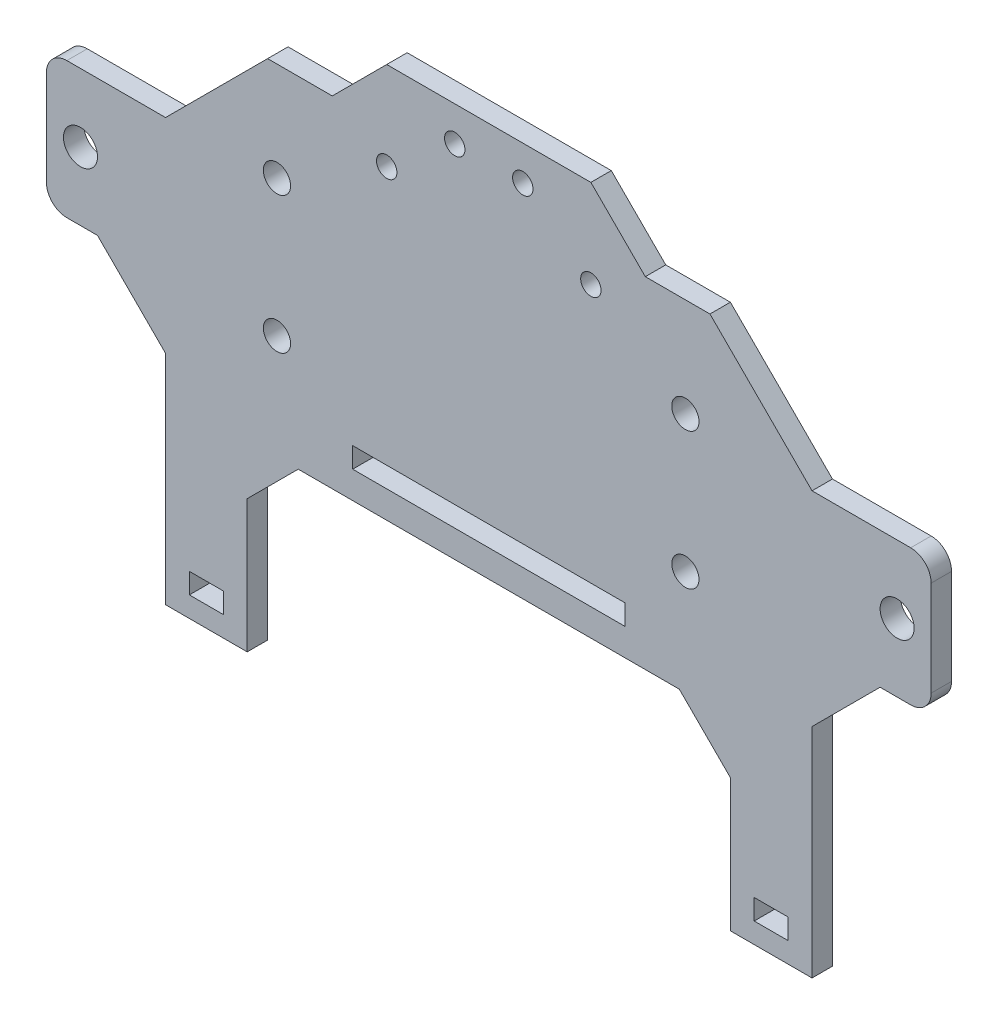
SolidWorks part; units mm, degrees
ref_plane "Front" through (0, 0, 0) normal (0, 0, 1) x (1, 0, 0)
ref_plane "Top" through (0, 0, 0) normal (0, 1, 0) x (1, 0, 0)
ref_plane "Right" through (0, 0, 0) normal (1, 0, 0) x (0, 0, -1)
sketch "Sketch1" plane through (0, 0, 0) normal (0, 0, 1) x (1, 0, 0)
  line L0 (40.5, -40) -> (44.5, -40)
  line L1 (44.5, -40) -> (47.5, -37)
  line L2 (47.5, -37) -> (47.5, 10)
  line L3 (52.5, 15) -> (70, 15)
  line L4 (75, 20) -> (75, 60)
  line L5 (70, 65) -> (-70, 65)
  line L6 (-75, 60) -> (-75, 20)
  line L7 (-70, 15) -> (-52.5, 15)
  line L8 (-47.5, 10) -> (-47.5, -37)
  line L9 (-47.5, -37) -> (-44.5, -40)
  line L10 (-44.5, -40) -> (-40.5, -40)
  line L11 (-40.5, -40) -> (-37.5, -37)
  line L12 (-37.5, -37) -> (-37.5, 10)
  line L13 (-32.5, 15) -> (32.5, 15)
  line L14 (37.5, 10) -> (37.5, -37)
  line L15 (37.5, -37) -> (40.5, -40)
  line L16 (0, 15) -> (0, 65) construction
  line L17 (-52.5, 15) -> (-47.5, 15)
  line L18 (-47.5, 15) -> (-47.5, 10)
  line L19 (52.5, 15) -> (47.5, 15)
  line L20 (47.5, 15) -> (47.5, 10)
  circle A0 centre (-42.5, -20) radius 1.5
  circle A1 centre (-42.5, -35) radius 1.5
  circle A2 centre (42.5, -20) radius 1.5
  circle A3 centre (42.5, -35) radius 1.5
  arc A5 (70, 15) -> (75, 20) centre (70, 20) ccw
  arc A6 (75, 60) -> (70, 65) centre (70, 60) ccw
  arc A7 (-70, 65) -> (-75, 60) centre (-70, 60) ccw
  arc A8 (-75, 20) -> (-70, 15) centre (-70, 20) ccw
  arc A10 (-32.5, 15) -> (-37.5, 10) centre (-32.5, 10) ccw
  arc A11 (37.5, 10) -> (32.5, 15) centre (32.5, 10) ccw
  circle A12 centre (60, 40) radius 2.5
  circle A14 centre (15, 60) radius 1.5
  circle A15 centre (-15, 60) radius 1.5
  circle A17 centre (-60, 40) radius 2.5
  point P28 (42.5, -9.2526)
  dimension "D2" = 5
  dimension "D3" = 15
  dimension "D4" = 3
  dimension "D7" = 15
  dimension "D8" = 5
  dimension "D10" = 5
  dimension "D15" = 5
  dimension "D17" = 5
  dimension "D1" = 150
  dimension "D11" = 50
  dimension "D12" = 27.5
  dimension "D13" = 140
  dimension "D14" = 40
  dimension "D16" = 40
  dimension "D18" = 5
  dimension "D19" = 5
extrude "Boss-Extrude1" add sketch "Sketch1" along normal blind 3
sketch "Sketch3" plane through (0, 0, 3) normal (0, 0, 1) x (1, 0, 0)
  line L0 (75, 27.5) -> (84.1937, 27.5) construction
  line L1 (65, 50) -> (65, 30)
  line L2 (75, 32.3641) -> (75, 23.0348)
  line L3 (47.5, 15) -> (75, 15)
  line L4 (47.5, 15) -> (47.5, 30)
  line L5 (47.5, 30) -> (65, 30)
  line L6 (75, 15) -> (75, 23.0348)
  line L7 (75, 65) -> (75, 32.3641)
  line L8 (47.5, 50) -> (65, 50)
  line L9 (47.5, 65) -> (47.5, 50)
  line L10 (47.5, 65) -> (75, 65)
  line L11 (0, 15) -> (0, 24.3681) construction
  line L12 (-32.5, 15) -> (32.5, 15) construction
  line L13 (-75, 27.5) -> (-84.1937, 27.5) construction
  line L14 (-47.5, 65) -> (-75, 65)
  line L15 (-47.5, 65) -> (-47.5, 50)
  line L16 (-47.5, 50) -> (-65, 50)
  line L17 (-75, 65) -> (-75, 32.3641)
  line L18 (-75, 15) -> (-75, 23.0348)
  line L19 (-47.5, 30) -> (-65, 30)
  line L20 (-47.5, 15) -> (-47.5, 30)
  line L21 (-47.5, 15) -> (-75, 15)
  line L24 (-75, 32.3641) -> (-75, 23.0348)
  line L26 (-65, 50) -> (-65, 30)
  dimension "D2" = 10
  dimension "D3" = 27.5
  dimension "D4" = 50
  dimension "D5" = 15
extrude "Cut-Extrude1" cut sketch "Sketch3" against normal blind 3
fillet "Fillet1" radius 3 4 edges at (65, 50, 1.5) (65, 30, 1.5) (-65, 50, 1.5) (-65, 30, 1.5)
chamfer "Chamfer4" distance 15 angle 45 2 edges at (47.5, 65, 1.5) (-47.5, 65, 1.5)
chamfer "Chamfer5" distance 10 angle 45 2 edges at (47.5, 30, 1.5) (-47.5, 30, 1.5)
sketch "Sketch6" plane through (0, 0, 3) normal (0, 0, 1) x (1, 0, 0)
  line L0 (-62, 50) -> (-47.5, 63)
  line L1 (-47.5, 63) -> (-32.5, 65)
  line L2 (0, 65) -> (0, 56.0032) construction
  line L3 (32.5, 65) -> (-32.5, 65) construction
  line L4 (-62, 50) -> (-47.5, 50) construction
  line L5 (-32.5, 65) -> (-47.5, 50) construction
  line L6 (-62, 50) -> (-47.5, 50)
  line L7 (-32.5, 65) -> (-47.5, 50)
  line L8 (32.5, 65) -> (47.5, 50)
  line L9 (62, 50) -> (47.5, 50)
  line L10 (47.5, 63) -> (32.5, 65)
  line L11 (62, 50) -> (47.5, 63)
  dimension "D1" = 13
sketch "Sketch13" plane through (0, 0, 3) normal (0, 0, 1) x (1, 0, 0)
  line L0 (32.5, 65) -> (-32.5, 65) construction
  line L1 (-15, 65) -> (15, 65)
  line L2 (-15, 65) -> (-15, 73)
  line L3 (-15, 73) -> (15, 73)
  line L4 (15, 65) -> (15, 73)
  dimension "D1" = 8
extrude "Boss-Extrude5" add sketch "Sketch13" against normal blind 3
sketch "Sketch8" plane through (0, 0, 3) normal (0, 0, 1) x (1, 0, 0)
  line L1 (-47.5, 20) -> (47.5, 20)
  line L2 (-47.5, 20) -> (-47.5, -45.3047)
  line L3 (-47.5, -45.3047) -> (47.5, -45.3047)
  line L4 (47.5, 20) -> (47.5, -45.3047)
extrude "Cut-Extrude5" cut sketch "Sketch8" against normal blind 10
sketch "Sketch11" plane through (0, 0, 3) normal (0, 0, 1) x (1, 0, 0)
  line L1 (-47.5, 20) -> (47.5, 20)
  line L2 (-47.5, 20) -> (-47.5, 13)
  line L3 (-47.5, 13) -> (47.5, 13)
  line L4 (47.5, 20) -> (47.5, 13)
  dimension "D1" = 7
extrude "Boss-Extrude3" add sketch "Sketch11" against normal blind 3
sketch "Sketch10" plane through (0, 0, 3) normal (0, 0, 1) x (1, 0, 0)
  line L7 (0, 63.3) -> (0, 65) construction
  line L10 (-47.5, 13) -> (47.5, 13) construction
  line L11 (-30, 13) -> (-28, 15)
  line L12 (-28, 15) -> (28, 15)
  line L13 (28, 15) -> (30, 13)
  line L14 (-30, 13) -> (30, 13)
  circle A0 centre (5, 67.89) radius 1.5
  circle A1 centre (-5, 67.89) radius 1.5
  circle A2 centre (-5, 18.11) radius 1.5
  circle A3 centre (5, 18.11) radius 1.5
  point P0 (0, 43)
  dimension "D4" = 3
  dimension "D5" = 5
  dimension "D3" = 30
  dimension "D7" = 2
  dimension "D8" = 30
  dimension "D9" = 30
  dimension "D10" = 2
extrude "Cut-Extrude6" cut sketch "Sketch10" against normal blind 3
sketch "Sketch12" plane through (0, 0, 3) normal (0, 0, 1) x (1, 0, 0)
  line L0 (47.5, 13) -> (47.5, -12)
  line L1 (47.5, -12) -> (35.5, -12)
  line L2 (35.5, -12) -> (35.5, 7.5)
  line L3 (30, 13) -> (47.5, 13) construction
  line L4 (35.5, 13) -> (47.5, 13)
  line L5 (0, 0) -> (0, 10.0543) construction
  line L6 (-35.5, 13) -> (-47.5, 13)
  line L7 (-35.5, -12) -> (-35.5, 7.5)
  line L8 (-47.5, -12) -> (-35.5, -12)
  line L9 (-47.5, 13) -> (-47.5, -12)
  line L10 (-30, 13) -> (-35.5, 7.5)
  line L11 (30, 13) -> (35.5, 7.5)
  line L12 (35.5, 13) -> (30, 13)
  line L13 (-30, 13) -> (-35.5, 13)
  dimension "D1" = 25
  dimension "D2" = 12
extrude "Boss-Extrude4" add sketch "Sketch12" against normal blind 3
chamfer "Chamfer6" distance 8 angle 45 2 edges at (15, 65, 1.5) (-15, 65, 1.5)
sketch "Sketch15" plane through (0, 0, 0) normal (0, 0, -1) x (-1, 0, 0)
  line L0 (0, -86.2349) -> (0, 116.2349) construction
  line L2 (-28, 15) -> (28, 15) construction
  line L3 (20, 19) -> (-20, 19)
  line L4 (20, 19) -> (20, 22)
  line L5 (20, 22) -> (-20, 22)
  line L6 (-20, 19) -> (-20, 22)
  line L7 (20, 19) -> (-20, 22) construction
  line L8 (20, 22) -> (-20, 19) construction
  point P0 (0, 20.5)
  point P3 (0, 15)
  dimension "D1" = 40
  dimension "D2" = 3
  dimension "D3" = 4
sketch "Sketch17" plane through (0, 0, 0) normal (0, 0, -1) x (-1, 0, 0)
  circle A0 centre (-28.888, 50.4888) radius 2
  circle A1 centre (-28.888, 30.4072) radius 2
  circle A2 centre (31.1268, 30.4072) radius 2
  circle A3 centre (31.1268, 50.4888) radius 2
  point P0 (-28.888, 50.4888)
  point P1 (-28.888, 30.4072)
  point P2 (31.1268, 30.4072)
  point P3 (31.1268, 50.4888)
extrude "Cut-Extrude9" cut sketch "Sketch17" against normal blind 10
extrude "Cut-Extrude8" cut sketch "Sketch15" against normal blind 10
sketch "Sketch16" plane through (0, 0, 0) normal (0, 0, -1) x (-1, 0, 0)
  line L0 (3.7926, 19) -> (6.2074, 19)
  line L2 (-6.2074, 19) -> (-3.7926, 19)
  arc A0 (6.2074, 19) -> (3.7926, 19) centre (5, 18.11) cw
  arc A1 (-3.7926, 19) -> (-6.2074, 19) centre (-5, 18.11) cw
  arc A2 (-6.2074, 19) -> (-3.7926, 19) centre (-5, 18.11) ccw construction
extrude "Boss-Extrude6" add sketch "Sketch16" against normal blind 3
sketch "Sketch18" plane through (0, 0, 0) normal (0, 0, -1) x (-1, 0, 0)
  line L0 (-134.2761, 21.4473) -> (-134.2761, 18.4473)
  line L1 (-39, -6) -> (-44, -6)
  line L2 (-39, -6) -> (-39, -9)
  line L3 (-39, -9) -> (-44, -9)
  line L4 (-44, -6) -> (-44, -9)
  line L5 (-39, -6) -> (-44, -9) construction
  line L6 (-39, -9) -> (-44, -6) construction
  line L11 (-129.2761, 21.4473) -> (-129.2761, 18.4473)
  line L12 (-129.2761, 21.4473) -> (-134.2761, 21.4473)
  line L13 (-129.2761, 18.4473) -> (-134.2761, 18.4473)
  line L14 (44, -9) -> (39, -9)
  line L15 (44, -6) -> (44, -9)
  line L16 (39, -6) -> (39, -9)
  line L17 (44, -6) -> (39, -6)
  line L18 (47.5, -12) -> (35.5, -12) construction
  line L19 (-35.5, -12) -> (-47.5, -12) construction
  point P0 (-41.5, -7.5)
  dimension "D1" = 3
  dimension "D2" = 5
  dimension "D3" = 3
  dimension "D4" = 3
extrude "Cut-Extrude11" cut sketch "Sketch18" against normal blind 10
